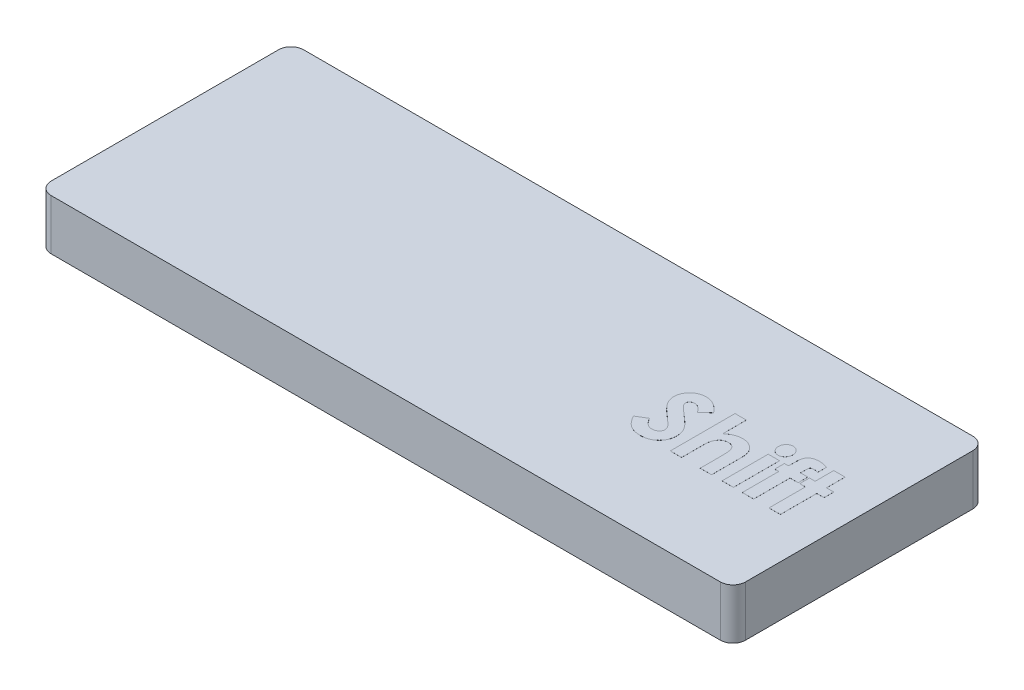
SolidWorks part; units mm, degrees
ref_plane "Front Plane" through (0, 0, 0) normal (0, 0, 1) x (1, 0, 0)
ref_plane "Top Plane" through (0, 0, 0) normal (0, 1, 0) x (1, 0, 0)
ref_plane "Right Plane" through (0, 0, 0) normal (1, 0, 0) x (0, 0, -1)
sketch "Sketch1" plane through (0, 0, 0) normal (0, 1, 0) x (1, 0, 0)
  line L0 (0, 0) -> (34.925, 0)
  line L1 (34.925, 0) -> (34.925, 12.7)
  line L2 (34.925, 12.7) -> (0, 12.7)
  line L3 (0, 12.7) -> (0, 0)
  dimension "D1" = 34.925
  dimension "D2" = 12.7
extrude "Boss-Extrude1" add sketch "Sketch1" along normal blind 2.54
fillet "Fillet1" radius 0.635 4 edges at (0, 1.27, -12.7) (34.925, 1.27, -12.7) (34.925, 1.27, 0) (0, 1.27, 0)
shell "Shell1" thickness 0.635 removed face at (17.4625, 0, -6.35)
sketch "Sketch2" plane through (0, 1.905, 0) normal (0, -1, 0) x (-1, 0, 0)
  line L0 (-0.635, 6.35) -> (-34.29, 6.35) construction
  line L1 (-0.635, 12.065) -> (-0.635, 0.635) construction
  line L2 (-34.29, 0.635) -> (-34.29, 12.065) construction
  line L3 (-17.4625, 0.635) -> (-17.4625, 12.065) construction
  line L4 (-0.635, 0.635) -> (-34.29, 0.635) construction
  line L5 (-34.29, 12.065) -> (-0.635, 12.065) construction
  circle A0 centre (-17.4625, 6.35) radius 2.54
  dimension "D1" = 5.08
extrude "Boss-Extrude2" add sketch "Sketch2" along normal up to surface (1.905 mm away) up to face at (17.4625, 0, -6.35)
sketch "Sketch3" plane through (0, 2.54, 0) normal (0, 1, 0) x (1, 0, 0)
  line L0 (34.925, 0.635) -> (34.925, 12.065) construction
  line L1 (0.635, 0) -> (34.29, 0) construction
  text T0 "<b>Shift</b>"
  dimension "D1" = 10.16
  dimension "D2" = 4.445
extrude "Boss-Extrude3" add sketch "Sketch3" along normal blind 0.0025
